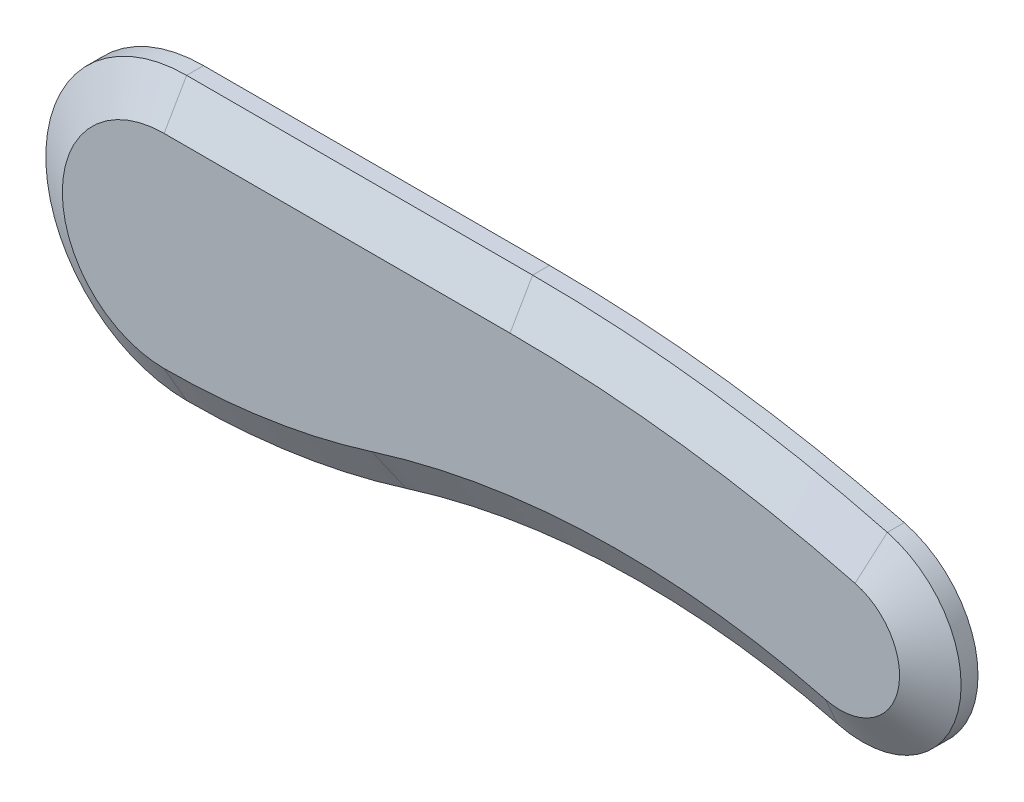
SolidWorks part; units mm, degrees
ref_plane "Front Plane" through (0, 0, 0) normal (0, 0, 1) x (1, 0, 0)
ref_plane "Top Plane" through (0, 0, 0) normal (0, 1, 0) x (1, 0, 0)
ref_plane "Right Plane" through (0, 0, 0) normal (1, 0, 0) x (0, 0, -1)
sketch "Sketch1" plane through (0, 0, 0) normal (0, 0, 1) x (1, 0, 0)
  line L0 (0, 0) -> (120, 0) construction
  line L1 (0, 0) -> (0, -25) construction
  line L2 (0, 25) -> (61.4231, 25)
  circle A0 centre (0, 0) radius 25
  circle A2 centre (120, 0) radius 17.5
  arc A3 (61.4231, 25) -> (124.409, 16.9355) centre (61.4231, -225) cw
  arc A4 (0, -25) -> (38.9734, -19.0205) centre (0, 105) ccw
  arc A5 (38.9734, -19.0205) -> (115.6605, -16.9534) centre (80.9448, -152.5809) cw
  dimension "D2" = 50
  dimension "D4" = 35
  dimension "D5" = 250
  dimension "D6" = 140
  dimension "D7" = 130
  dimension "D1" = 120
  dimension "D3" = 0
extrude "Boss-Extrude1" add sketch "Sketch1" along normal blind 7 contours A0 L0 A2 A3 L2 | L0 A0 A4 A5 A2 | A0 | A2 region at (60.7118, 4.4003, 0) region at (0, 0, 0) region at (120, 0, 0)
chamfer "Chamfer1" distance 4 angle 60 6 edges at (19.7147, -23.4964, 7) (-25, 0, 7) (30.7116, 25, 7) (93.1732, 22.9757, 7) (136.9445, -4.3742, 7) (77.1726, -12.6318, 7) first distance on face at (19.6007, -22.7533, 3.5) first distance on face at (-12.5, 0, 3.5) first distance on face at (30.7116, 25, 3.5) first distance on face at (93.0446, 21.9717, 3.5) first distance on face at (128.4896, -2.1916, 3.5) first distance on face at (77.2448, -15.3094, 3.5)
sketch "Sketch3" plane through (0, 0, 0) normal (0, 0, -1) x (-1, 0, 0)
  circle A0 centre (0, 0) radius 8.5
  circle A1 centre (-120, 0) radius 8.5
  dimension "D1" = 17
  dimension "D2" = 17
extrude "Cut-Extrude2" cut sketch "Sketch3" against normal blind 4
ref_plane "Plane1" through (0, 0, 2.5) normal (0, 0, -1) x (-1, 0, 0)
sketch "Sketch5" plane through (0, 0, 2.5) normal (0, 0, -1) x (-1, 0, 0)
  line L0 (0, 0) -> (-60, 0) construction
  line L1 (0, 0) -> (-83.9535, 13.2969) construction
  line L2 (0, 0) -> (-30.0702, -10.9446) construction
  line L3 (-86.0464, 16.9219) -> (-73.7677, 16.9219)
  line L4 (-81.8606, 9.6719) -> (-79.7677, 13.2969)
  line L5 (-79.7677, 13.2969) -> (-81.8606, 16.9219)
  line L6 (-81.8606, 16.9219) -> (-86.0464, 16.9219)
  line L7 (-86.0464, 16.9219) -> (-88.1393, 13.2969)
  line L8 (-88.1393, 13.2969) -> (-86.0464, 9.6719)
  line L9 (-86.0464, 9.6719) -> (-81.8606, 9.6719)
  line L10 (-57.9071, -3.625) -> (-55.8142, 0)
  line L11 (-55.8142, 0) -> (-57.9071, 3.625)
  line L12 (-57.9071, 3.625) -> (-62.0929, 3.625)
  line L13 (-62.0929, 3.625) -> (-64.1858, 0)
  line L14 (-64.1858, 0) -> (-62.0929, -3.625)
  line L15 (-62.0929, -3.625) -> (-57.9071, -3.625)
  line L16 (-27.9773, -14.5696) -> (-25.8844, -10.9446)
  line L17 (-25.8844, -10.9446) -> (-27.9773, -7.3196)
  line L18 (-27.9773, -7.3196) -> (-32.1631, -7.3196)
  line L19 (-32.1631, -7.3196) -> (-34.256, -10.9446)
  line L20 (-34.256, -10.9446) -> (-32.1631, -14.5696)
  line L21 (-32.1631, -14.5696) -> (-27.9773, -14.5696)
  line L22 (-86.0464, 9.6719) -> (-73.7677, 9.6719)
  line L23 (-73.7677, 16.9219) -> (-73.7677, 9.6719) construction
  line L24 (-62.0929, 3.625) -> (-49.8142, 3.625)
  line L25 (-62.0929, -3.625) -> (-49.8142, -3.625)
  line L26 (-49.8142, 3.625) -> (-49.8142, -3.625) construction
  line L27 (-32.1631, -7.3196) -> (-19.8844, -7.3196)
  line L28 (-32.1631, -14.5696) -> (-19.8844, -14.5696)
  line L29 (-19.8844, -14.5696) -> (-19.8844, -7.3196) construction
  circle A0 centre (-83.9535, 13.2969) radius 3.625 construction
  circle A1 centre (-60, 0) radius 3.625 construction
  circle A2 centre (-30.0702, -10.9446) radius 3.625 construction
  circle A3 centre (-73.7677, 13.2969) radius 6
  circle A4 centre (-49.8142, 0) radius 6
  circle A5 centre (-19.8844, -10.9446) radius 6
  circle A6 centre (-83.9535, 13.2969) radius 2.125
  circle A7 centre (-60, 0) radius 2.125
  circle A8 centre (-30.0702, -10.9446) radius 2.125
  dimension "D7" = 12
  dimension "D8" = 4.25
  dimension "D1" = 20
  dimension "D2" = 9
  dimension "D3" = 85
  dimension "D4" = 60
  dimension "D5" = 32
  dimension "D6" = 7.25
extrude "Cut-Extrude3" cut sketch "Sketch5" against normal blind 3.5 contours L8 L9 L4 L5 L3 L7 | A3 | A3 L3 L5 | A3 L4 L22 | L14 L15 L10 L11 L12 L13 | A4 L24 L11 | A4 L10 L25 | A4 | A5 | A5 L16 L28 | A5 L27 L17 | L20 L21 L16 L17 L18 L19 | A7 | A8 | A6 region at (83.9535, 16.8112, 2.5) region at (80.1796, 15.8006, 2.5) region at (73.7677, 13.2969, 2.5) region at (80.1796, 10.7933, 2.5) region at (60, -3.5143, 2.5) region at (56.2261, -2.5037, 2.5) region at (56.2261, 2.5037, 2.5) region at (49.8142, 0, 2.5) region at (30.0702, -14.4589, 2.5) region at (26.2963, -13.4483, 2.5) region at (26.2963, -8.441, 2.5) region at (19.8844, -10.9446, 2.5) region at (60, 0, 2.5) region at (30.0702, -10.9446, 2.5)
extrude "Cut-Extrude4" cut sketch "Sketch5<3>" along normal through all contours A3 | A4 | A5 | A6 | A7 | A8 region at (73.7677, 13.2969, 2.5) region at (49.8142, 0, 2.5) region at (19.8844, -10.9446, 2.5) region at (83.9535, 13.2969, 2.5) region at (60, 0, 2.5) region at (30.0702, -10.9446, 2.5)
sketch "Sketch5<3>" plane through (0, 0, 2.5) normal (0, 0, -1) x (-1, 0, 0) same geometry as "Sketch5"
chamfer "Chamfer2" distance 0.5 angle 70 3 edges at (67.7677, 13.2969, 6) (13.8844, -10.9446, 6) (43.8142, 0, 6) first distance on face at (76.1583, 13.2969, 4.25) first distance on face at (22.2749, -10.9446, 4.25) first distance on face at (52.2048, 0, 4.25)
sketch "Sketch7" plane through (0, 0, 0) normal (0, 0, -1) x (-1, 0, 0)
  circle A0 centre (0, 0) radius 9.5
  circle A1 centre (0, 0) radius 8.5 construction
  circle A2 centre (0, 0) radius 8.5
  circle A3 centre (-120, 0) radius 8.5 construction
  circle A4 centre (-120, 0) radius 8.5
  circle A5 centre (-120, 0) radius 9.5
  dimension "D1" = 1
  dimension "D2" = 1
extrude "Boss-Extrude2" add sketch "Sketch7" along normal blind 0.5
